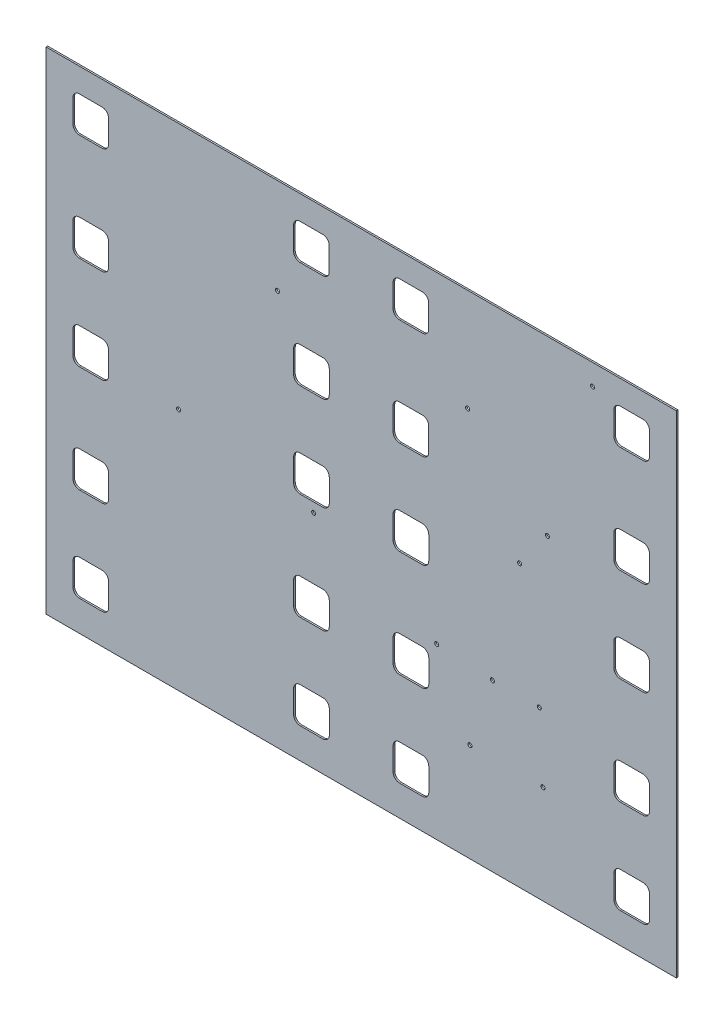
SolidWorks part; units mm, degrees
material "ABS"
ref_plane "X-Y Datum" through (0, 0, 0) normal (0, 0, 1) x (1, 0, 0)
ref_plane "X-Z Datum" through (0, 0, 0) normal (0, 1, 0) x (1, 0, 0)
ref_plane "Y-Z Datum" through (0, 0, 0) normal (1, 0, 0) x (0, 0, -1)
sketch "Sketch9" plane through (0, 0, 0) normal (0, 0, 1) x (1, 0, 0)
  line L0 (-82.7559, -182.5893) -> (-82.7583, -160.1613) construction
  line L1 (-89.109, -153.8119) -> (-111.537, -153.8143) construction
  line L2 (-117.8863, -160.165) -> (-117.8839, -182.593) construction
  line L3 (-111.5333, -188.9423) -> (-89.1053, -188.9399) construction
  line L4 (476.934, -311.4483) -> (476.8831, 172.8027)
  line L5 (476.8831, 172.8027) -> (-144.3755, 172.7375)
  line L6 (-144.3755, 172.7375) -> (-144.3246, -311.5135)
  line L7 (-144.3246, -311.5135) -> (476.934, -311.4483)
  line L8 (476.934, -311.4483) -> (476.8831, 172.8027)
  line L9 (476.8831, 172.8027) -> (-144.3755, 172.7375)
  line L10 (-144.3755, 172.7375) -> (-144.3246, -311.5135)
  line L11 (-144.3246, -311.5135) -> (476.934, -311.4483)
  line L12 (-111.5443, -83.8117) -> (-89.1163, -83.8093) construction
  line L13 (-82.767, -77.4587) -> (-82.7693, -55.0307) construction
  line L14 (-89.12, -48.6813) -> (-111.548, -48.6837) construction
  line L15 (-117.8973, -55.0344) -> (-117.895, -77.4624) construction
  line L16 (-82.7877, 120.2549) -> (-82.7901, 142.6829) construction
  line L17 (-89.1408, 149.0323) -> (-111.5688, 149.0299) construction
  line L18 (-117.9181, 142.6792) -> (-117.9157, 120.2512) construction
  line L19 (-111.5651, 113.9019) -> (-89.1371, 113.9043) construction
  line L20 (-111.554, 8.7713) -> (-89.126, 8.7737) construction
  line L21 (-117.9071, 37.5486) -> (-117.9047, 15.1206) construction
  line L22 (-89.1297, 43.9017) -> (-111.5577, 43.8993) construction
  line L23 (-82.7767, 15.1243) -> (-82.7791, 37.5523) construction
  line L24 (-82.7559, -182.5893) -> (-82.7583, -160.1613)
  line L25 (-89.109, -153.8119) -> (-111.537, -153.8143)
  line L26 (-117.8863, -160.165) -> (-117.8839, -182.593)
  line L27 (-111.5333, -188.9423) -> (-89.1053, -188.9399)
  line L28 (-111.5443, -83.8117) -> (-89.1163, -83.8093)
  line L29 (-82.767, -77.4587) -> (-82.7693, -55.0307)
  line L30 (-89.12, -48.6813) -> (-111.548, -48.6837)
  line L31 (-117.8973, -55.0344) -> (-117.895, -77.4624)
  line L32 (-82.7877, 120.2549) -> (-82.7901, 142.6829)
  line L33 (-89.1408, 149.0323) -> (-111.5688, 149.0299)
  line L34 (-117.9181, 142.6792) -> (-117.9157, 120.2512)
  line L35 (-111.5651, 113.9019) -> (-89.1371, 113.9043)
  line L36 (-111.554, 8.7713) -> (-89.126, 8.7737)
  line L37 (-117.9071, 37.5486) -> (-117.9047, 15.1206)
  line L38 (-89.1297, 43.9017) -> (-111.5577, 43.8993)
  line L39 (-82.7767, 15.1243) -> (-82.7791, 37.5523)
  line L40 (-82.7462, -275.1723) -> (-82.7486, -252.7443) construction
  line L41 (-89.0992, -246.3949) -> (-111.5272, -246.3973) construction
  line L42 (-117.8766, -252.748) -> (-117.8742, -275.176) construction
  line L43 (-111.5235, -281.5253) -> (-89.0955, -281.5229) construction
  line L44 (-82.7462, -275.1723) -> (-82.7486, -252.7443)
  line L45 (-89.0992, -246.3949) -> (-111.5272, -246.3973)
  line L46 (-117.8766, -252.748) -> (-117.8742, -275.176)
  line L47 (-111.5235, -281.5253) -> (-89.0955, -281.5229)
  arc A0 (-89.1053, -188.9399) -> (-82.7559, -182.5893) centre (-89.1059, -182.5899) ccw construction
  arc A1 (-82.7583, -160.1613) -> (-89.109, -153.8119) centre (-89.1083, -160.1619) ccw construction
  arc A2 (-111.537, -153.8143) -> (-117.8863, -160.165) centre (-111.5363, -160.1643) ccw construction
  arc A3 (-117.8839, -182.593) -> (-111.5333, -188.9423) centre (-111.5339, -182.5923) ccw construction
  arc A4 (-89.1163, -83.8093) -> (-82.767, -77.4587) centre (-89.117, -77.4593) ccw construction
  arc A5 (-82.7693, -55.0307) -> (-89.12, -48.6813) centre (-89.1193, -55.0313) ccw construction
  arc A6 (-111.548, -48.6837) -> (-117.8973, -55.0344) centre (-111.5473, -55.0337) ccw construction
  arc A7 (-117.895, -77.4624) -> (-111.5443, -83.8117) centre (-111.545, -77.4617) ccw construction
  arc A8 (-89.1371, 113.9043) -> (-82.7877, 120.2549) centre (-89.1377, 120.2543) ccw construction
  arc A9 (-82.7901, 142.6829) -> (-89.1408, 149.0323) centre (-89.1401, 142.6823) ccw construction
  arc A10 (-111.5688, 149.0299) -> (-117.9181, 142.6792) centre (-111.5681, 142.6799) ccw construction
  arc A11 (-117.9157, 120.2512) -> (-111.5651, 113.9019) centre (-111.5657, 120.2519) ccw construction
  arc A12 (-82.7791, 37.5523) -> (-89.1297, 43.9017) centre (-89.1291, 37.5517) ccw construction
  arc A13 (-89.126, 8.7737) -> (-82.7767, 15.1243) centre (-89.1267, 15.1237) ccw construction
  arc A14 (-117.9047, 15.1206) -> (-111.554, 8.7713) centre (-111.5547, 15.1213) ccw construction
  arc A15 (-111.5577, 43.8993) -> (-117.9071, 37.5486) centre (-111.5571, 37.5493) ccw construction
  arc A16 (-89.1053, -188.9399) -> (-82.7559, -182.5893) centre (-89.1059, -182.5899) ccw
  arc A17 (-82.7583, -160.1613) -> (-89.109, -153.8119) centre (-89.1083, -160.1619) ccw
  arc A18 (-111.537, -153.8143) -> (-117.8863, -160.165) centre (-111.5363, -160.1643) ccw
  arc A19 (-117.8839, -182.593) -> (-111.5333, -188.9423) centre (-111.5339, -182.5923) ccw
  arc A20 (-89.1163, -83.8093) -> (-82.767, -77.4587) centre (-89.117, -77.4593) ccw
  arc A21 (-82.7693, -55.0307) -> (-89.12, -48.6813) centre (-89.1193, -55.0313) ccw
  arc A22 (-111.548, -48.6837) -> (-117.8973, -55.0344) centre (-111.5473, -55.0337) ccw
  arc A23 (-117.895, -77.4624) -> (-111.5443, -83.8117) centre (-111.545, -77.4617) ccw
  arc A24 (-89.1371, 113.9043) -> (-82.7877, 120.2549) centre (-89.1377, 120.2543) ccw
  arc A25 (-82.7901, 142.6829) -> (-89.1408, 149.0323) centre (-89.1401, 142.6823) ccw
  arc A26 (-111.5688, 149.0299) -> (-117.9181, 142.6792) centre (-111.5681, 142.6799) ccw
  arc A27 (-117.9157, 120.2512) -> (-111.5651, 113.9019) centre (-111.5657, 120.2519) ccw
  arc A28 (-82.7791, 37.5523) -> (-89.1297, 43.9017) centre (-89.1291, 37.5517) ccw
  arc A29 (-89.126, 8.7737) -> (-82.7767, 15.1243) centre (-89.1267, 15.1237) ccw
  arc A30 (-117.9047, 15.1206) -> (-111.554, 8.7713) centre (-111.5547, 15.1213) ccw
  arc A31 (-111.5577, 43.8993) -> (-117.9071, 37.5486) centre (-111.5571, 37.5493) ccw
  arc A32 (-89.0955, -281.5229) -> (-82.7462, -275.1723) centre (-89.0962, -275.1729) ccw construction
  arc A33 (-111.5272, -246.3973) -> (-117.8766, -252.748) centre (-111.5266, -252.7473) ccw construction
  arc A34 (-117.8742, -275.176) -> (-111.5235, -281.5253) centre (-111.5242, -275.1753) ccw construction
  arc A35 (-89.0955, -281.5229) -> (-82.7462, -275.1723) centre (-89.0962, -275.1729) ccw
  arc A36 (-111.5272, -246.3973) -> (-117.8766, -252.748) centre (-111.5266, -252.7473) ccw
  arc A37 (-117.8742, -275.176) -> (-111.5235, -281.5253) centre (-111.5242, -275.1753) ccw
  arc A38 (-82.7486, -252.7443) -> (-89.0992, -246.3949) centre (-89.0986, -252.7449) ccw construction
  arc A39 (-82.7486, -252.7443) -> (-89.0992, -246.3949) centre (-89.0986, -252.7449) ccw
  dimension "D1" = 0
extrude "Boss-Extrude2" add sketch "Sketch9" along normal blind 1.5875 contours L10 L11 L8 L9 A39 L44 A35 L47 A37 L46 A36 L45 A31 L38 A28 L39 A29 L36 A30 L37 A27 L34 A26 L33 A25 L32 A24 L35 A23 L31 A22 L30 A21 L29 A20 L28 A19 L26 A18 L25 A17 L24 A16 L27 | L44 A39 L45 A36 L46 A37 L47 A35 | L26 A19 L27 A16 L24 A17 L25 A18 | L38 A31 L37 A30 L36 A29 L39 A28 | L34 A27 L35 A24 L32 A25 L33 A26 | L31 A23 L28 A20 L29 A21 L30 A22 region at (171.7018, -69.3676, 0) region at (-100.3211, -171.3771, 0) region at (-100.3322, -66.2465, 0) region at (-100.3529, 131.4671, 0) region at (-100.3419, 26.3365, 0) region at (-100.3114, -263.9601, 0)
sketch "Sketch10" plane through (0, 0, 1.5875) normal (0, 0, 1) x (1, 0, 0)
  line L4 (476.934, -311.4483) -> (476.8831, 172.8027)
  line L5 (476.8831, 172.8027) -> (-144.3755, 172.7375)
  line L6 (-144.3755, 172.7375) -> (-144.3246, -311.5135)
  line L7 (-144.3246, -311.5135) -> (476.934, -311.4483)
  line L8 (476.934, -311.4483) -> (476.8831, 172.8027)
  line L9 (476.8831, 172.8027) -> (-144.3755, 172.7375)
  line L10 (-144.3755, 172.7375) -> (-144.3246, -311.5135)
  line L11 (-144.3246, -311.5135) -> (476.934, -311.4483)
  line L12 (-117.8863, -160.165) -> (-117.8839, -182.593)
  line L13 (-111.5333, -188.9423) -> (-89.1053, -188.9399)
  line L14 (-82.7559, -182.5893) -> (-82.7583, -160.1613)
  line L15 (-89.109, -153.8119) -> (-111.537, -153.8143)
  line L16 (-117.8863, -160.165) -> (-117.8839, -182.593)
  line L17 (-111.5333, -188.9423) -> (-89.1053, -188.9399)
  line L18 (-82.7559, -182.5893) -> (-82.7583, -160.1613)
  line L19 (-89.109, -153.8119) -> (-111.537, -153.8143)
  line L20 (-117.8766, -252.748) -> (-117.8742, -275.176)
  line L21 (-89.0992, -246.3949) -> (-111.5272, -246.3973)
  line L22 (-82.7462, -275.1723) -> (-82.7486, -252.7443)
  line L23 (-111.5235, -281.5253) -> (-89.0955, -281.5229)
  line L24 (-117.8766, -252.748) -> (-117.8742, -275.176)
  line L25 (-89.0992, -246.3949) -> (-111.5272, -246.3973)
  line L26 (-82.7462, -275.1723) -> (-82.7486, -252.7443)
  line L27 (-111.5235, -281.5253) -> (-89.0955, -281.5229)
  line L28 (-89.12, -48.6813) -> (-111.548, -48.6837)
  line L29 (-117.8973, -55.0344) -> (-117.895, -77.4624)
  line L30 (-111.5443, -83.8117) -> (-89.1163, -83.8093)
  line L31 (-82.767, -77.4587) -> (-82.7693, -55.0307)
  line L32 (-89.12, -48.6813) -> (-111.548, -48.6837)
  line L33 (-117.8973, -55.0344) -> (-117.895, -77.4624)
  line L34 (-111.5443, -83.8117) -> (-89.1163, -83.8093)
  line L35 (-82.767, -77.4587) -> (-82.7693, -55.0307)
  line L36 (-82.7877, 120.2549) -> (-82.7901, 142.6829)
  line L37 (-111.5651, 113.9019) -> (-89.1371, 113.9043)
  line L38 (-117.9181, 142.6792) -> (-117.9157, 120.2512)
  line L39 (-89.1408, 149.0323) -> (-111.5688, 149.0299)
  line L40 (-82.7877, 120.2549) -> (-82.7901, 142.6829)
  line L41 (-111.5651, 113.9019) -> (-89.1371, 113.9043)
  line L42 (-117.9181, 142.6792) -> (-117.9157, 120.2512)
  line L43 (-89.1408, 149.0323) -> (-111.5688, 149.0299)
  line L44 (-111.554, 8.7713) -> (-89.126, 8.7737)
  line L45 (-82.7767, 15.1243) -> (-82.7791, 37.5523)
  line L46 (-89.1297, 43.9017) -> (-111.5577, 43.8993)
  line L47 (-117.9071, 37.5486) -> (-117.9047, 15.1206)
  line L48 (-111.554, 8.7713) -> (-89.126, 8.7737)
  line L49 (-82.7767, 15.1243) -> (-82.7791, 37.5523)
  line L50 (-89.1297, 43.9017) -> (-111.5577, 43.8993)
  line L51 (-117.9071, 37.5486) -> (-117.9047, 15.1206)
  arc A4 (-117.8839, -182.593) -> (-111.5333, -188.9423) centre (-111.5339, -182.5923) ccw
  arc A5 (-89.1053, -188.9399) -> (-82.7559, -182.5893) centre (-89.1059, -182.5899) ccw
  arc A6 (-82.7583, -160.1613) -> (-89.109, -153.8119) centre (-89.1083, -160.1619) ccw
  arc A7 (-111.537, -153.8143) -> (-117.8863, -160.165) centre (-111.5363, -160.1643) ccw
  arc A8 (-117.8839, -182.593) -> (-111.5333, -188.9423) centre (-111.5339, -182.5923) ccw
  arc A9 (-89.1053, -188.9399) -> (-82.7559, -182.5893) centre (-89.1059, -182.5899) ccw
  arc A10 (-82.7583, -160.1613) -> (-89.109, -153.8119) centre (-89.1083, -160.1619) ccw
  arc A11 (-111.537, -153.8143) -> (-117.8863, -160.165) centre (-111.5363, -160.1643) ccw
  arc A12 (-111.5272, -246.3973) -> (-117.8766, -252.748) centre (-111.5266, -252.7473) ccw
  arc A13 (-82.7486, -252.7443) -> (-89.0992, -246.3949) centre (-89.0986, -252.7449) ccw
  arc A14 (-89.0955, -281.5229) -> (-82.7462, -275.1723) centre (-89.0962, -275.1729) ccw
  arc A15 (-117.8742, -275.176) -> (-111.5235, -281.5253) centre (-111.5242, -275.1753) ccw
  arc A16 (-111.5272, -246.3973) -> (-117.8766, -252.748) centre (-111.5266, -252.7473) ccw
  arc A17 (-82.7486, -252.7443) -> (-89.0992, -246.3949) centre (-89.0986, -252.7449) ccw
  arc A18 (-89.0955, -281.5229) -> (-82.7462, -275.1723) centre (-89.0962, -275.1729) ccw
  arc A19 (-117.8742, -275.176) -> (-111.5235, -281.5253) centre (-111.5242, -275.1753) ccw
  arc A20 (-111.548, -48.6837) -> (-117.8973, -55.0344) centre (-111.5473, -55.0337) ccw
  arc A21 (-117.895, -77.4624) -> (-111.5443, -83.8117) centre (-111.545, -77.4617) ccw
  arc A22 (-89.1163, -83.8093) -> (-82.767, -77.4587) centre (-89.117, -77.4593) ccw
  arc A23 (-82.7693, -55.0307) -> (-89.12, -48.6813) centre (-89.1193, -55.0313) ccw
  arc A24 (-111.548, -48.6837) -> (-117.8973, -55.0344) centre (-111.5473, -55.0337) ccw
  arc A25 (-117.895, -77.4624) -> (-111.5443, -83.8117) centre (-111.545, -77.4617) ccw
  arc A26 (-89.1163, -83.8093) -> (-82.767, -77.4587) centre (-89.117, -77.4593) ccw
  arc A27 (-82.7693, -55.0307) -> (-89.12, -48.6813) centre (-89.1193, -55.0313) ccw
  arc A28 (-89.1371, 113.9043) -> (-82.7877, 120.2549) centre (-89.1377, 120.2543) ccw
  arc A29 (-117.9157, 120.2512) -> (-111.5651, 113.9019) centre (-111.5657, 120.2519) ccw
  arc A30 (-111.5688, 149.0299) -> (-117.9181, 142.6792) centre (-111.5681, 142.6799) ccw
  arc A31 (-82.7901, 142.6829) -> (-89.1408, 149.0323) centre (-89.1401, 142.6823) ccw
  arc A32 (-89.1371, 113.9043) -> (-82.7877, 120.2549) centre (-89.1377, 120.2543) ccw
  arc A33 (-117.9157, 120.2512) -> (-111.5651, 113.9019) centre (-111.5657, 120.2519) ccw
  arc A34 (-111.5688, 149.0299) -> (-117.9181, 142.6792) centre (-111.5681, 142.6799) ccw
  arc A35 (-82.7901, 142.6829) -> (-89.1408, 149.0323) centre (-89.1401, 142.6823) ccw
  arc A36 (-89.126, 8.7737) -> (-82.7767, 15.1243) centre (-89.1267, 15.1237) ccw
  arc A37 (-82.7791, 37.5523) -> (-89.1297, 43.9017) centre (-89.1291, 37.5517) ccw
  arc A38 (-111.5577, 43.8993) -> (-117.9071, 37.5486) centre (-111.5571, 37.5493) ccw
  arc A39 (-117.9047, 15.1206) -> (-111.554, 8.7713) centre (-111.5547, 15.1213) ccw
  arc A40 (-89.126, 8.7737) -> (-82.7767, 15.1243) centre (-89.1267, 15.1237) ccw
  arc A41 (-82.7791, 37.5523) -> (-89.1297, 43.9017) centre (-89.1291, 37.5517) ccw
  arc A42 (-111.5577, 43.8993) -> (-117.9071, 37.5486) centre (-111.5571, 37.5493) ccw
  arc A43 (-117.9047, 15.1206) -> (-111.554, 8.7713) centre (-111.5547, 15.1213) ccw
  dimension "D1" = 0
  dimension "D2" = 0
  dimension "D3" = 0
  dimension "D4" = 0
  dimension "D5" = 0
  dimension "D6" = 0
extrude "Cut-Extrude6" cut sketch "Sketch10" against normal through all contours L40 A35 L43 A34 L42 A33 L41 A32 | L51 A43 L48 A40 L49 A41 L50 A42 | L35 A27 L32 A24 L33 A25 L34 A26 | L19 A11 L16 A8 L17 A9 L18 A10 | L24 A19 L27 A18 L26 A17 L25 A16 region at (-100.3211, -171.3771, 1.5875) region at (-100.3114, -263.9601, 1.5875) region at (-100.3322, -66.2465, 1.5875) region at (-100.3529, 131.4671, 1.5875) region at (-100.3419, 26.3365, 1.5875)
pattern_linear "LPattern2" count 2 spacing 217.5764 along (1, 0.0001, 0) of "Cut-Extrude6"
ref_plane "Plane1" through (166.272, 0.0175, 0) normal (-1, -0.0001, 0) x (0, 0, 1)
mirror "Mirror1" about plane through (166.272, 0.0175, 0) normal (-1, -0.0001, 0) of "LPattern2", "Cut-Extrude6"
sketch "Sketch11" plane through (0, 0, 1.5875) normal (0, 0, 1) x (1, 0, 0)
  circle A3 centre (295.6543, -147.9548) radius 1.9939
  circle A5 centre (295.6543, -147.9548) radius 1.9939
  circle A7 centre (394.3353, 152.1565) radius 1.9939
  circle A9 centre (394.3353, 152.1565) radius 1.9939
  circle A11 centre (271.1937, 71.8561) radius 1.9939
  circle A13 centre (271.1937, 71.8561) radius 1.9939
  circle A15 centre (83.7969, 78.6239) radius 1.9939
  circle A17 centre (83.7969, 78.6239) radius 1.9939
  circle A19 centre (-13.7373, -71.3863) radius 1.9939
  circle A21 centre (-13.7373, -71.3863) radius 1.9939
  circle A23 centre (349.9245, 2.4389) radius 1.9939
  circle A44 centre (349.9245, 2.4389) radius 1.9939
  circle A45 centre (322.4284, -34.688) radius 1.9939
  circle A46 centre (322.4284, -34.688) radius 1.9939
  circle A47 centre (341.8543, -147.95) radius 1.9939
  circle A48 centre (341.8543, -147.95) radius 1.9939
  circle A49 centre (345.5113, -214.3496) radius 1.9939
  circle A50 centre (345.5113, -214.3496) radius 1.9939
  circle A51 centre (119.4061, -93.0712) radius 1.9939
  circle A52 centre (119.4061, -93.0712) radius 1.9939
  circle A53 centre (240.6965, -144.4935) radius 1.9939
  circle A54 centre (240.6965, -144.4935) radius 1.9939
  circle A55 centre (273.5113, -214.3572) radius 1.9939
  circle A56 centre (273.5113, -214.3572) radius 1.9939
  dimension "D1" = 0
  dimension "D2" = 0
  dimension "D3" = 0
  dimension "D4" = 0
  dimension "D5" = 0
  dimension "D6" = 0
  dimension "D7" = 0
  dimension "D8" = 0
  dimension "D9" = 0
  dimension "D10" = 0
  dimension "D11" = 0
  dimension "D12" = 0
extrude "Cut-Extrude7" cut sketch "Sketch11" against normal through all
